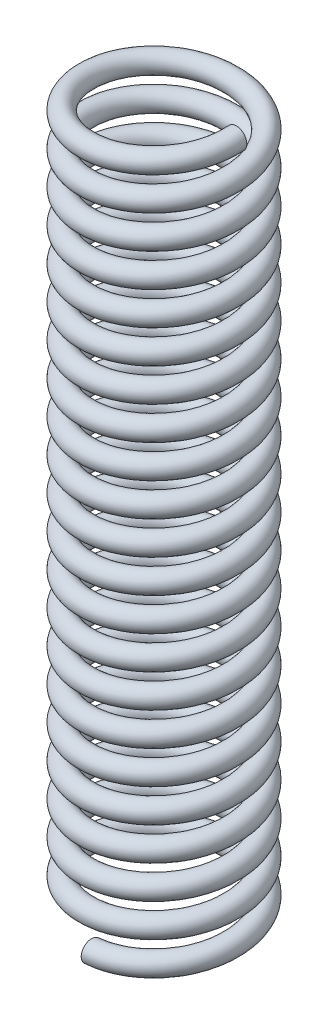
SolidWorks part; units mm, degrees
note: '?' marks a value the reader was unsure of.
material "AISI 304"
ref_plane "Front Plane" through (0, 0, 0) normal (0, 0, 1) x (1, 0, 0)
ref_plane "Top Plane" through (0, 0, 0) normal (0, 1, 0) x (1, 0, 0)
ref_plane "Right Plane" through (0, 0, 0) normal (1, 0, 0) x (0, 0, -1)
ref_axis "SpringAxis" through (0, 1.15, 0) along (0, -1, 0)?
sketch "SpringBodyDiameterS" plane through (0, 0, 0) normal (0, 0, 1) x (1, 0, 0)
  line L0 (0, 0) -> (1.5, 0) construction
  line L1 (0, 0) -> (0, 1) construction
  line L2 (1.75, 0) -> (2, 0) construction
  circle A0 centre (1.75, 0) radius 0.25
  dimension "WireDia" = 0.5
  dimension "RefRevolve" = 1
  dimension "RevolveDia" = 3.5
  dimension "RefID" = 1.5
  dimension "RefOD" = 2
sketch "SpringHelixS" plane through (0, 0, 0) normal (0, 1, 0) x (1, 0, 0)
  circle A0 centre (0, 0) radius 1.75
  dimension "RefDia" = 3.5
curve "SPRING HELIX" pitch 0.8 height 17 turns 21.25 parameters "Height"=17, "Pitch"=0.8
sweep "SPRING" add profiles "SpringBodyDiameterS" path "SPRING HELIX"
